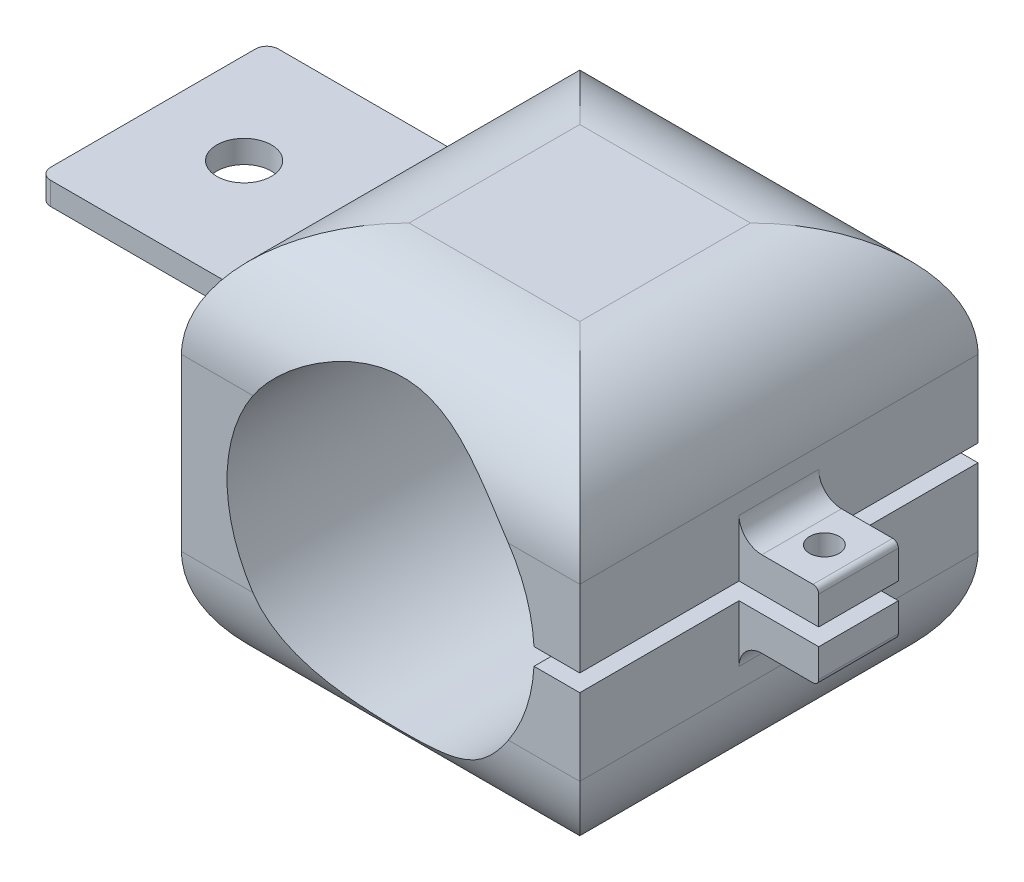
SolidWorks part; units mm, degrees
ref_plane "Front Plane" through (0, 0, 0) normal (0, 0, 1) x (1, 0, 0)
ref_plane "Top Plane" through (0, 0, 0) normal (0, 1, 0) x (1, 0, 0)
ref_plane "Right Plane" through (0, 0, 0) normal (1, 0, 0) x (0, 0, -1)
sketch "Sketch1" plane through (0, 0, 0) normal (0, 0, 1) x (1, 0, 0)
  line L0 (13.4792, 0.75) -> (17.5, 0.75)
  line L1 (17.5, -17.5) -> (-17.5, -17.5)
  line L2 (17.5, -17.5) -> (17.5, -0.75)
  line L3 (17.5, 17.5) -> (-17.5, 17.5)
  line L4 (-17.5, -17.5) -> (-17.5, 17.5)
  line L5 (17.5, -17.5) -> (-17.5, 17.5) construction
  line L6 (17.5, 17.5) -> (-17.5, -17.5) construction
  line L7 (13.4792, -0.75) -> (17.5, -0.75)
  line L8 (16.0003, 0.75) -> (16.0003, 17.5) construction
  line L9 (16.0003, -0.75) -> (16.0003, -17.5) construction
  line L10 (17.5, 0.75) -> (17.5, 17.5)
  arc A0 (13.4792, 0.75) -> (13.4792, -0.75) centre (0, 0) ccw
  dimension "D1" = 27
  dimension "D2" = 35
  dimension "D3" = 1.5
extrude "Boss-Extrude1" add sketch "Sketch1" along normal blind 35
sketch "Sketch3" plane through (0, 0.75, 0) normal (0, -1, 0) x (1, 0, 0)
  line L0 (17.5, 35) -> (17.5, 0) construction
  line L1 (17.5, 21) -> (24.5, 21)
  line L2 (17.5, 21) -> (17.5, 14)
  line L3 (17.5, 14) -> (24.5, 14)
  line L4 (24.5, 21) -> (24.5, 14)
  line L5 (17.5, 14) -> (17.5, 0) construction
  line L6 (17.5, 21) -> (17.5, 35) construction
  dimension "D1" = 7
  dimension "D2" = 7
extrude "Boss-Extrude2" add sketch "Sketch3" against normal blind 3
fillet "Fillet1" radius 2 1 edges at (17.5, 3.75, 17.5)
fillet "Fillet2" radius 0.5 1 edges at (24.5, 3.75, 17.5)
sketch "Sketch4" plane through (0, 3.75, 0) normal (0, 1, 0) x (1, 0, 0)
  line L0 (21.5, -17.5) -> (21.5, -14) construction
  line L1 (19.5, -14) -> (24, -14) construction
  line L2 (21.5, -17.5) -> (21.5, -21) construction
  line L3 (24, -21) -> (19.5, -21) construction
  line L4 (21.5, -17.5) -> (17.5, -17.5) construction
  line L5 (17.5, -35) -> (17.5, 0) construction
  point P0 (21.5, -17.5)
  dimension "D1" = 4
hole_wizard "M2 Clearance Hole1" positions "Sketch5" profile "Sketch6" hole size "M2" standard "ANSI Metric" end condition up to next
sketch "Sketch5" plane through (0, 3.75, 0) normal (0, 1, 0) x (1, 0, 0)
  point P0 (21.5, -17.5)
sketch "Sketch6" plane through (21.5, 3.75, 17.5) normal (1, 0, 0) x (0, 0, 1)
  line L0 (0, 0) -> (0, 3)
  line L1 (0, 3) -> (1.3, 3)
  line L2 (1.3, 3) -> (1.3, 0)
  line L5 (1.3, 0) -> (0, 0)
  line L11 (0, -6.35) -> (0, 107.95) construction
  dimension "Thru Hole Dia." = 2.6
  dimension "Thru Hole Depth" = 3
mirror "Mirror3" about plane through (0, 0, 0) normal (0, 1, 0) of "Boss-Extrude2"
mirror "Mirror5" about plane through (0, 0, 0) normal (0, 1, 0) of "M2 Clearance Hole1"
fillet "Fillet3" radius 0.5 1 edges at (24.5, -3.75, 17.5)
fillet "Fillet4" radius 2 1 edges at (17.5, -3.75, 17.5)
fillet "Fillet5" radius 10 8 edges at (0, -17.5, 35) (17.5, -17.5, 17.5) (0, -17.5, 0) (-17.5, -17.5, 17.5) (0, 17.5, 0) (-17.5, 17.5, 17.5) (0, 17.5, 35) (17.5, 17.5, 17.5)
sketch "Sketch8" plane through (-17.5, 0, 0) normal (-1, 0, 0) x (0, 0, 1)
  line L0 (35, 7.5) -> (0, 7.5) construction
  line L1 (7.5, 7.5) -> (27.5, 7.5)
  line L2 (7.5, 7.5) -> (7.5, 5.5)
  line L3 (7.5, 5.5) -> (27.5, 5.5)
  line L4 (27.5, 7.5) -> (27.5, 5.5)
  line L5 (7.5, 6.5) -> (0, 6.5) construction
  line L6 (0, 7.5) -> (0, -7.5) construction
  line L7 (27.5, 6.5) -> (35, 6.5) construction
  line L8 (35, 7.5) -> (35, -7.5) construction
  dimension "D1" = 2
  dimension "D2" = 20
extrude "Boss-Extrude4" add sketch "Sketch8" along normal blind 20
sketch "Sketch9" plane through (0, 7.5, 0) normal (0, 1, 0) x (1, 0, 0)
  line L0 (-17.5, -17.5) -> (-29.5, -17.5) construction
  line L1 (-17.5, -27.5) -> (-17.5, -7.5) construction
  line L2 (-29.5, -17.5) -> (-29.5, -7.5) construction
  line L3 (-37.5, -7.5) -> (-17.5, -7.5) construction
  line L4 (-29.5, -17.5) -> (-29.5, -27.5) construction
  line L5 (-37.5, -27.5) -> (-17.5, -27.5) construction
  dimension "D1" = 12
hole_wizard "M4 Clearance Hole1" positions "Sketch10" profile "Sketch11" hole size "M4" standard "ANSI Metric" end condition up to next
sketch "Sketch10" plane through (0, 7.5, 0) normal (0, 1, 0) x (1, 0, 0)
  point P0 (-29.5, -17.5)
sketch "Sketch11" plane through (-29.5, 7.5, 17.5) normal (1, 0, 0) x (0, 0, 1)
  line L0 (0, 0) -> (0, 2)
  line L1 (0, 2) -> (2.4, 2)
  line L2 (2.4, 2) -> (2.4, 0)
  line L5 (2.4, 0) -> (0, 0)
  line L11 (0, -6.35) -> (0, 107.95) construction
  dimension "Thru Hole Dia." = 4.8
  dimension "Thru Hole Depth" = 2
fillet "Fillet6" radius 3 2 edges at (-17.5, 7.5, 17.5) (-17.5, 5.5, 17.5)
fillet "Fillet7" radius 1 2 edges at (-37.5, 6.5, 7.5) (-37.5, 6.5, 27.5)
